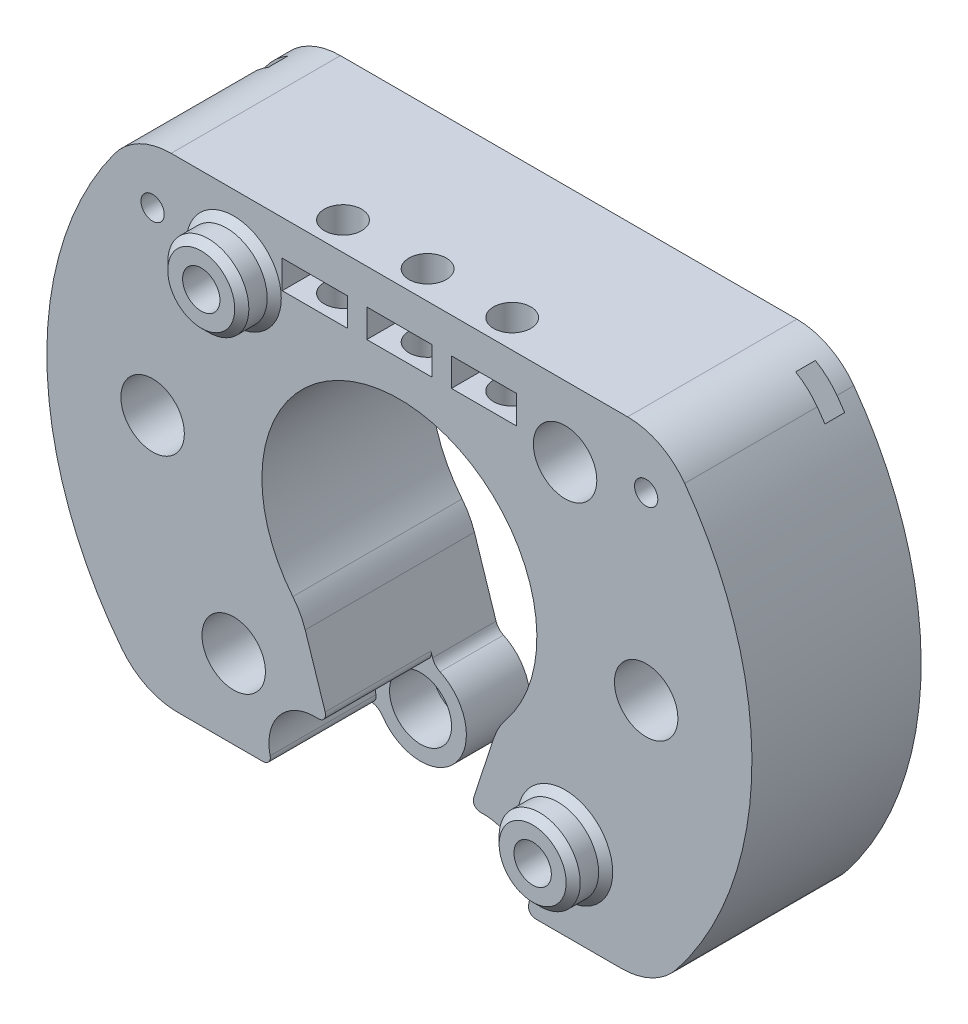
SolidWorks part; units mm, degrees
ref_plane "Ebene vorne" through (0, 0, 0) normal (0, 0, 1) x (1, 0, 0)
ref_plane "Ebene oben" through (0, 0, 0) normal (0, 1, 0) x (1, 0, 0)
ref_plane "Ebene rechts" through (0, 0, 0) normal (1, 0, 0) x (0, 0, -1)
sketch "Skizze1" plane through (0, 0, 0) normal (0, 0, 1) x (1, 0, 0)
  line L0 (0, 15.499) -> (0, -28.3741) construction
  line L1 (0, 33.5) -> (-37.1181, 33.5)
  line L2 (0, 33.5) -> (37.1181, 33.5)
  line L3 (-36, -34.6987) -> (-36, -65)
  line L4 (-36, -65) -> (0, -65)
  line L5 (-50, 78.1636) -> (-50, -33.9451) construction
  line L6 (50, 78.1636) -> (50, -33.9451) construction
  line L7 (-50, 0) -> (50, 0) construction
  line L8 (36, -34.6987) -> (36, -65)
  line L10 (0, -65) -> (36, -65)
  line L11 (-17.9133, -34.6987) -> (-36, -34.6987)
  line L12 (-23.5, 23.5) -> (23.5, 23.5) construction
  line L13 (-23.5, 23.5) -> (-23.5, -23.5) construction
  line L14 (-23.5, -23.5) -> (23.5, -23.5) construction
  line L15 (23.5, 23.5) -> (23.5, -23.5) construction
  line L18 (-14, -13.5739) -> (-10, -25.8153)
  line L19 (14, -13.5739) -> (10, -25.8153)
  line L22 (36, -34.6987) -> (17.9133, -34.6987)
  arc A0 (-37.1181, 33.5) -> (-36, -34.6987) centre (0, 0) ccw
  circle A1 centre (0, 0) radius 19.5
  arc A3 (37.1181, 33.5) -> (36, -34.6987) centre (0, 0) cw
  circle A4 centre (-23.5, 23.5) radius 4.5
  circle A5 centre (23.5, 23.5) radius 4.5
  circle A6 centre (23.5, -23.5) radius 4.5
  circle A7 centre (-23.5, -23.5) radius 4.5
  arc A8 (-10, -25.8153) -> (-17.9133, -34.6987) centre (-12, -32) cw
  arc A9 (10, -25.8153) -> (17.9133, -34.6987) centre (12, -32) ccw
  circle A10 centre (23.5, -23.5) radius 4.5
  point P18 (0, 0)
  point P37 (-23.5, 0)
  point P38 (0, 23.5)
  dimension "D1" = 72
  dimension "D4" = 39
  dimension "D2" = 47
  dimension "D7" = 9
  dimension "D8" = 28
  dimension "D13" = 32
  dimension "D10" = 6.5
  dimension "D3" = 65
  dimension "D5" = 33.5
  dimension "D6" = 100
  dimension "D9" = 24
  dimension "D14" = 20
extrude "Aufsatz-Linear austragen1" add sketch "Skizze1" along normal blind 24 contours L19 A9 L22 A3 L2 L1 A0 A8 L18 A1 A7 A6 A5 A4 region at (18.559, 32.2678, 0)
sketch "Skizze2" plane through (0, 0, 24) normal (0, 0, 1) x (1, 0, 0)
  line L3 (0, 0) -> (0, -32) construction
  circle A0 centre (12, -32) radius 6.5
  arc A1 (10, -25.8153) -> (17.9133, -34.6987) centre (12, -32) ccw construction
  circle A3 centre (-12, -32) radius 6.5
  arc A4 (-17.9133, -34.6987) -> (-10, -25.8153) centre (-12, -32) ccw construction
extrude "Schnitt-Linear austragen1" cut sketch "Skizze2" against normal blind 15
sketch "Skizze3" plane through (0, 0, 9) normal (0, 0, 1) x (1, 0, 0)
  circle A0 centre (12, -32) radius 4.4
  circle A1 centre (-12, -32) radius 4.4
  dimension "D1" = 8.8
extrude "Schnitt-Linear austragen2" cut sketch "Skizze3" against normal blind 6
sketch "Skizze4" plane through (0, 0, 24) normal (0, 0, 1) x (1, 0, 0)
  circle A0 centre (-23.5, 23.5) radius 5.75
  circle A1 centre (23.5, -23.5) radius 5.75
  circle A6 centre (-23.5, 23.5) radius 2.65
  circle A7 centre (23.5, -23.5) radius 2.65
  dimension "D1" = 11.5
  dimension "D2" = 5.3
extrude "Aufsatz-Linear austragen2" add sketch "Skizze4" along normal blind 4.6 and the other way blind 2
sketch "Skizze8" plane through (0, 33.5, 0) normal (0, 1, 0) x (1, 0, 0)
  line L0 (-37.1181, -24) -> (37.1181, -24) construction
  line L1 (4.6188, -20) -> (2.3094, -16)
  line L2 (2.3094, -16) -> (-2.3094, -16)
  line L3 (-2.3094, -16) -> (-4.6188, -20)
  line L4 (-4.6188, -20) -> (-2.3094, -24) construction
  line L5 (-2.3094, -24) -> (2.3094, -24) construction
  line L6 (2.3094, -24) -> (4.6188, -20) construction
  line L7 (-4.6188, -20) -> (-4.6188, -24)
  line L8 (-4.6188, -24) -> (4.6188, -24)
  line L9 (4.6188, -24) -> (4.6188, -20)
  line L10 (0, 0) -> (0, -24) construction
  line L11 (-37.1181, 0) -> (37.1181, 0) construction
  line L18 (16.6188, -20) -> (14.3094, -16)
  line L19 (14.3094, -16) -> (9.6906, -16)
  line L20 (9.6906, -16) -> (7.3812, -20)
  line L21 (7.3812, -20) -> (7.3812, -24)
  line L22 (7.3812, -24) -> (16.6188, -24)
  line L23 (16.6188, -24) -> (16.6188, -20)
  line L24 (7.3812, -20) -> (9.6906, -24) construction
  line L25 (9.6906, -24) -> (14.3094, -24) construction
  line L26 (14.3094, -24) -> (16.6188, -20) construction
  line L27 (4.6188, -20) -> (16.6188, -20) construction
  line L28 (-7.3812, -20) -> (-9.6906, -16)
  line L29 (-9.6906, -16) -> (-14.3094, -16)
  line L30 (-14.3094, -16) -> (-16.6188, -20)
  line L31 (-16.6188, -20) -> (-16.6188, -24)
  line L32 (-16.6188, -24) -> (-7.3812, -24)
  line L33 (-7.3812, -24) -> (-7.3812, -20)
  line L34 (-16.6188, -20) -> (-14.3094, -24) construction
  line L35 (-14.3094, -24) -> (-9.6906, -24) construction
  line L36 (-9.6906, -24) -> (-7.3812, -20) construction
  line L37 (4.6188, -20) -> (-7.3812, -20) construction
  circle A0 centre (0, -20) radius 4 construction
  circle A1 centre (12, -20) radius 4 construction
  circle A2 centre (-12, -20) radius 4 construction
  dimension "D1" = 8
  dimension "D2" = 2
  dimension "D3" = 12
  dimension "D4" = 12
extrude "Schnitt-Linear austragen6" cut sketch "Skizze8" against normal blind 4 from offset 5 offset against normal yes
sketch "Skizze9" plane through (0, 33.5, 0) normal (0, 1, 0) x (1, 0, 0)
  circle A0 centre (-12, -20) radius 2.65
  circle A1 centre (0, -20) radius 2.65
  circle A2 centre (12, -20) radius 2.65
  dimension "D1" = 5.3
extrude "Schnitt-Linear austragen7" cut sketch "Skizze9" against normal blind 30
sketch "Skizze12" plane through (0, 0, 0) normal (0, 0, -1) x (-1, 0, 0)
  line L0 (0, 0) -> (0, 33.5) construction
  line L1 (37.1181, 33.5) -> (-37.1181, 33.5) construction
  circle A0 centre (-35, 25.5) radius 1.65
  circle A1 centre (35, 25.5) radius 1.65
  dimension "D1" = 3.3
  dimension "D2" = 70
  dimension "D3" = 8
extrude "Schnitt-Linear austragen9" cut sketch "Skizze12" against normal up to next
sketch "Skizze11" plane through (0, 0, 0) normal (0, 0, -1) x (-1, 0, 0)
  line L0 (0, 0) -> (0, 33.5) construction
  line L1 (37.1181, 33.5) -> (-37.1181, 33.5) construction
  line L2 (-44.8995, 39.6421) -> (-30.7574, 25.5)
  line L3 (-30.7574, 25.5) -> (-35, 21.2574)
  line L4 (-44.8995, 39.6421) -> (-49.1421, 35.3995)
  line L5 (-49.1421, 35.3995) -> (-35, 21.2574)
  line L6 (44.8995, 39.6421) -> (49.1421, 35.3995)
  line L7 (44.8995, 39.6421) -> (30.7574, 25.5)
  line L8 (30.7574, 25.5) -> (35, 21.2574)
  line L9 (49.1421, 35.3995) -> (35, 21.2574)
  dimension "D1" = 45
  dimension "D2" = 6
  dimension "D3" = 20
extrude "Schnitt-Linear austragen8" cut sketch "Skizze11" against normal blind 2.8 from offset 2.4 offset against normal yes
sketch "Skizze13" plane through (0, 0, 24) normal (0, 0, 1) x (1, 0, 0)
  line L0 (0, 33.5) -> (0, 0) construction
  line L1 (-37.1181, 33.5) -> (37.1181, 33.5) construction
  circle A0 centre (35, 0) radius 4.5
  circle A1 centre (-35, 0) radius 4.5
  dimension "D1" = 70
  dimension "D2" = 9
extrude "Schnitt-Linear austragen10" cut sketch "Skizze13" against normal up to next
chamfer "Fase1" distance 1 angle 45 4 edges at (29.25, -23.5, 28.6) (-17.75, 23.5, 28.6) (29.25, -23.5, 24) (-17.75, 23.5, 24)
fillet "Verrundung1" radius 10 6 edges at (-37.1181, 33.5, 12) (37.1181, 33.5, 12) (36, -34.6987, 12) (-36, -34.6987, 12) (14, -13.5739, 12) (-14, -13.5739, 12)
fillet "Verrundung2" radius 1 4 edges at (17.9133, -34.6987, 16.5) (-17.9133, -34.6987, 16.5) (-10, -25.8153, 16.5) (10, -25.8153, 16.5)
fillet "Verrundung4" radius 2 4 edges at (17.9133, -34.6987, 4.5) (10, -25.8153, 4.5) (-10, -25.8153, 4.5) (-17.9133, -34.6987, 4.5)
sketch "Skizze14" plane through (0, 0, 22) normal (0, 0, -1) x (-1, 0, 0)
  line L0 (-26.15, -19.863) -> (-26.15, -27.137)
  line L1 (-20.85, -19.863) -> (-20.85, -27.137)
  line L2 (20.85, 27.137) -> (20.85, 19.863)
  line L3 (26.15, 27.137) -> (26.15, 19.863)
  circle A0 centre (-23.5, -23.5) radius 4.5 construction
  arc A1 (-26.15, -27.137) -> (-20.85, -27.137) centre (-23.5, -23.5) ccw
  circle A2 centre (-23.5, -23.5) radius 2.65 construction
  arc A3 (-20.85, -19.863) -> (-26.15, -19.863) centre (-23.5, -23.5) ccw
  circle A4 centre (23.5, 23.5) radius 4.5 construction
  arc A5 (20.85, 19.863) -> (26.15, 19.863) centre (23.5, 23.5) ccw
  circle A6 centre (23.5, 23.5) radius 2.65 construction
  arc A7 (26.15, 27.137) -> (20.85, 27.137) centre (23.5, 23.5) ccw
extrude "Schnitt-Linear austragen11" cut sketch "Skizze14" against normal blind 0.2
sketch "Skizze18" plane through (0, 0, 22.2) normal (0, 0, -1) x (-1, 0, 0)
  line L6 (-20.85, -27.137) -> (-20.85, -19.863) construction
  line L7 (-26.15, -20.85) -> (-20.85, -20.85)
  line L8 (-26.15, -20.85) -> (-26.15, -26.15)
  line L9 (-26.15, -26.15) -> (-20.85, -26.15)
  line L10 (-20.85, -20.85) -> (-20.85, -26.15)
  line L11 (-26.15, -20.85) -> (-20.85, -26.15) construction
  line L12 (-26.15, -26.15) -> (-20.85, -20.85) construction
  line L13 (20.85, 27.137) -> (20.85, 19.863) construction
  line L14 (26.15, 26.15) -> (20.85, 26.15)
  line L15 (26.15, 26.15) -> (26.15, 20.85)
  line L16 (26.15, 20.85) -> (20.85, 20.85)
  line L17 (20.85, 26.15) -> (20.85, 20.85)
  line L18 (26.15, 26.15) -> (20.85, 20.85) construction
  line L19 (26.15, 20.85) -> (20.85, 26.15) construction
  point P0 (-23.5, -23.5)
  point P7 (23.5, 23.5)
extrude "Schnitt-Linear austragen14" cut sketch "Skizze18" against normal blind 0.2
sketch "Skizze19" plane through (0, 0, 5.2) normal (0, 0, -1) x (-1, 0, 0)
  line L0 (0, 33.5) -> (0, 0) construction
  line L1 (2.65, 33.5) -> (-2.65, 33.5) construction
  line L2 (-31.712, 26.4546) -> (-35.9546, 22.212)
  line L3 (-30.7574, 25.5) -> (-37.3998, 32.1424) construction
  line L4 (-41.5525, 27.8099) -> (-35, 21.2574) construction
  line L5 (-35.9546, 22.212) -> (-38.288, 24.5454)
  line L6 (-38.288, 24.5454) -> (-34.0454, 28.788)
  line L7 (-34.0454, 28.788) -> (-31.712, 26.4546)
  line L8 (34.0454, 28.788) -> (31.712, 26.4546)
  line L9 (38.288, 24.5454) -> (34.0454, 28.788)
  line L10 (35.9546, 22.212) -> (38.288, 24.5454)
  line L11 (31.712, 26.4546) -> (35.9546, 22.212)
  circle A0 centre (-35, 25.5) radius 1.65 construction
extrude "Schnitt-Linear austragen15" cut sketch "Skizze19" against normal blind 0.2
sketch "Skizze20" plane through (0, 0, 5.4) normal (0, 0, -1) x (-1, 0, 0)
  line L0 (0, 33.5) -> (0, 0) construction
  line L1 (2.65, 33.5) -> (-2.65, 33.5) construction
  line L2 (-35, 27.8335) -> (-37.3335, 25.5)
  line L3 (-34.0454, 28.788) -> (-36.1667, 26.6667) construction
  line L4 (-34.0454, 28.788) -> (-38.288, 24.5454) construction
  line L5 (-37.3335, 25.5) -> (-35, 23.1665)
  line L6 (-35.9546, 22.212) -> (-31.712, 26.4546) construction
  line L7 (-35, 23.1665) -> (-32.6665, 25.5)
  line L8 (-33.8333, 24.3333) -> (-31.712, 26.4546) construction
  line L9 (-32.6665, 25.5) -> (-35, 27.8335)
  line L10 (35, 23.1665) -> (32.6665, 25.5)
  line L11 (37.3335, 25.5) -> (35, 23.1665)
  line L12 (35, 27.8335) -> (37.3335, 25.5)
  line L13 (32.6665, 25.5) -> (35, 27.8335)
  arc A0 (-36.1667, 26.6667) -> (-33.8333, 24.3333) centre (-35, 25.5) ccw construction
extrude "Schnitt-Linear austragen16" cut sketch "Skizze20" against normal blind 0.2
